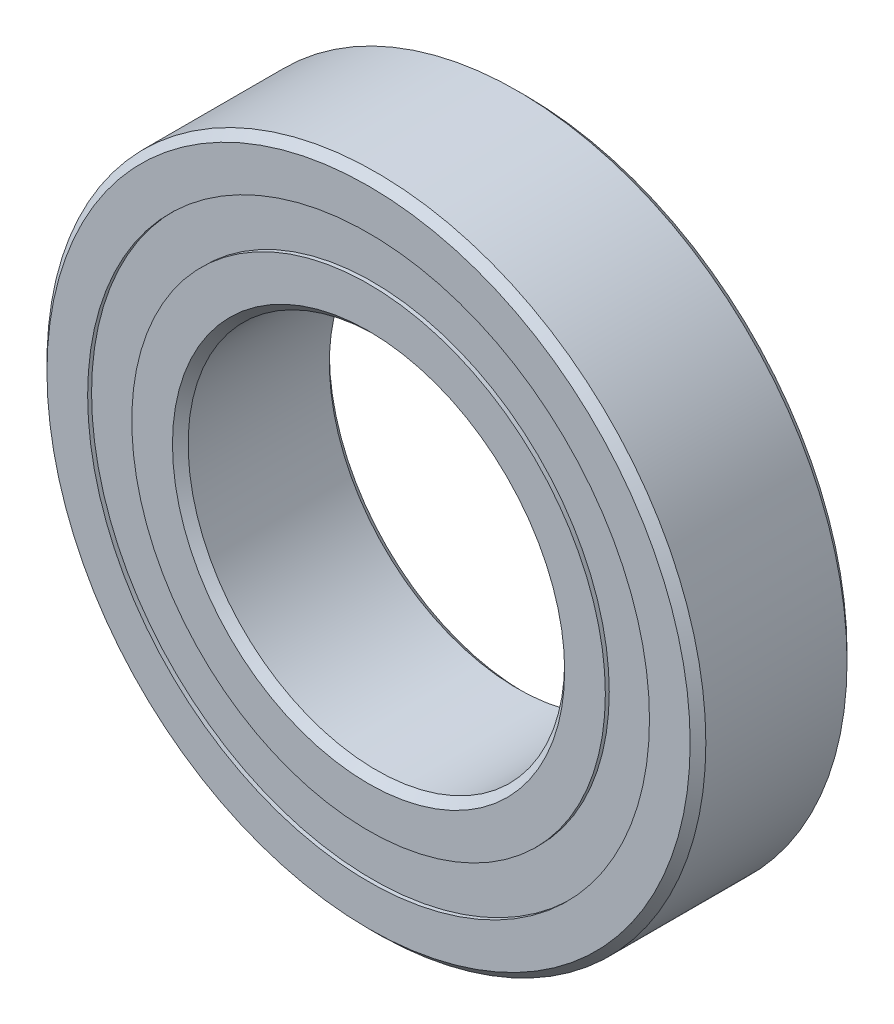
SolidWorks part; units mm, degrees
ref_plane "Front Plane" through (0, 0, 0) normal (0, 0, 1) x (1, 0, 0)
ref_plane "Top Plane" through (0, 0, 0) normal (0, 1, 0) x (1, 0, 0)
ref_plane "Right Plane" through (0, 0, 0) normal (1, 0, 0) x (0, 0, -1)
sketch "Sketch1" plane through (0, 0, 0) normal (1, 0, 0) x (0, 0, -1)
  line L0 (-2.5, 0) -> (2.5, 0) construction
  line L1 (0, 10.5) -> (0, -10.5) construction
  line L2 (2.25, 10.5) -> (-2.25, 10.5)
  line L3 (-2.25, 10.5) -> (-2.5, 10.25)
  line L4 (-2.5, 10.25) -> (-2.5, 8.9533)
  line L5 (-2.5, 8.9533) -> (-1.1111, 8.9533)
  line L6 (2.5, 8.9533) -> (1.1111, 8.9533)
  line L7 (2.5, 10.25) -> (2.5, 8.9533)
  line L8 (2.25, 10.5) -> (2.5, 10.25)
  line L9 (0, 10.5) -> (0, 8.25) construction
  line L10 (0, 8.25) -> (0, 6) construction
  arc A0 (-1.1111, 8.9533) -> (1.1111, 8.9533) centre (0, 8.25) cw
  point P14 (0, 6)
  dimension "D3" = 2.2222
  dimension "D1" = 45
  dimension "Width" = 5
  dimension "OD" = 21
  dimension "D2" = 0.25
  dimension "Shaft Dia" = 12
  dimension "D4" = 0.7033
revolve "Revolve1" add sketch "Sketch1" angle 360 about L0
sketch "Sketch3" plane through (0, 0, 0) normal (1, 0, 0) x (0, 0, -1)
  line L0 (-2.5, 7.5467) -> (-1.1111, 7.5467)
  line L1 (0, 10.5) -> (0, -10.5) construction
  line L2 (-2.5, 10.25) -> (-2.5, 8.9533) construction
  line L3 (-2.5, 7.5467) -> (-2.5, 6.25)
  line L4 (-2.25, 10.5) -> (-2.5, 10.25) construction
  line L5 (-2.5, 6.25) -> (-2.25, 6)
  line L6 (-2.25, 6) -> (2.25, 6)
  line L7 (2.25, 10.5) -> (2.25, -10.5) construction
  line L8 (2.25, 6) -> (2.5, 6.25)
  line L9 (2.5, -10.25) -> (2.5, 10.25) construction
  line L10 (2.5, 6.25) -> (2.5, 7.5467)
  line L11 (2.5, 7.5467) -> (1.1111, 7.5467)
  line L13 (2.25, 10.5) -> (2.5, 10.25) construction
  arc A0 (1.1111, 8.9533) -> (-1.1111, 8.9533) centre (0, 8.25) ccw construction
  arc A1 (1.1111, 7.5467) -> (-1.1111, 7.5467) centre (0, 8.25) cw
revolve "Revolve3" add sketch "Sketch3" angle 360 about L0
sketch "Sketch4" plane through (0, 0, 0) normal (1, 0, 0) x (0, 0, -1)
  line L0 (-1.315, 8.25) -> (1.315, 8.25)
  arc A2 (-1.315, 8.25) -> (1.315, 8.25) centre (0, 8.25) cw
  arc A3 (1.1111, 8.9533) -> (-1.1111, 8.9533) centre (0, 8.25) ccw construction
revolve "Revolve4" add sketch "Sketch4" angle 360 about L0
ref_axis "Axis1" through (0, 0, -2.5) along (0, 0, 1)
pattern_circular "CirPattern1" count 12 every 30 about axis through (0, 0, -2.5) along (0, 0, 1) of bodies 104
sketch "Sketch5" plane through (0, 0, 0) normal (1, 0, 0) x (0, 0, -1)
  line L0 (-2.5, 8.9533) -> (-1.1111, 8.9533) construction
  line L1 (-2.375, 8.9533) -> (-1.315, 8.9533)
  line L2 (-2.375, 8.9533) -> (-2.375, 7.5467)
  line L3 (-2.375, 7.5467) -> (-1.315, 7.5467)
  line L4 (-1.315, 8.9533) -> (-1.315, 7.5467)
  line L5 (-2.5, 7.5467) -> (-1.1111, 7.5467) construction
  line L6 (2.5, 8.9533) -> (1.1111, 8.9533) construction
  line L7 (2.375, 8.9533) -> (1.315, 8.9533)
  line L8 (2.375, 8.9533) -> (2.375, 7.5467)
  line L9 (2.375, 7.5467) -> (1.315, 7.5467)
  line L10 (1.315, 8.9533) -> (1.315, 7.5467)
  line L11 (2.5, 7.5467) -> (1.1111, 7.5467) construction
  line L12 (-2.25, 10.5) -> (-2.5, 10.25) construction
  point P18 (-2.375, 10.375)
revolve "Revolve5" add sketch "Sketch5" angle 360 about L0
equation "\"D2@Sketch1\" = \"Width@Sketch1\"*.05"
equation "\"D3@Sketch1\" = \"Width@Sketch1\"/2.25"
equation "\"D4@Sketch1\" = (((\"OD@Sketch1\"-\"Width@Sketch1\")/2)/3.25)/3.5"
equation "\"D2@CirPattern1\" = 360/\"Balls@CirPattern1\""
